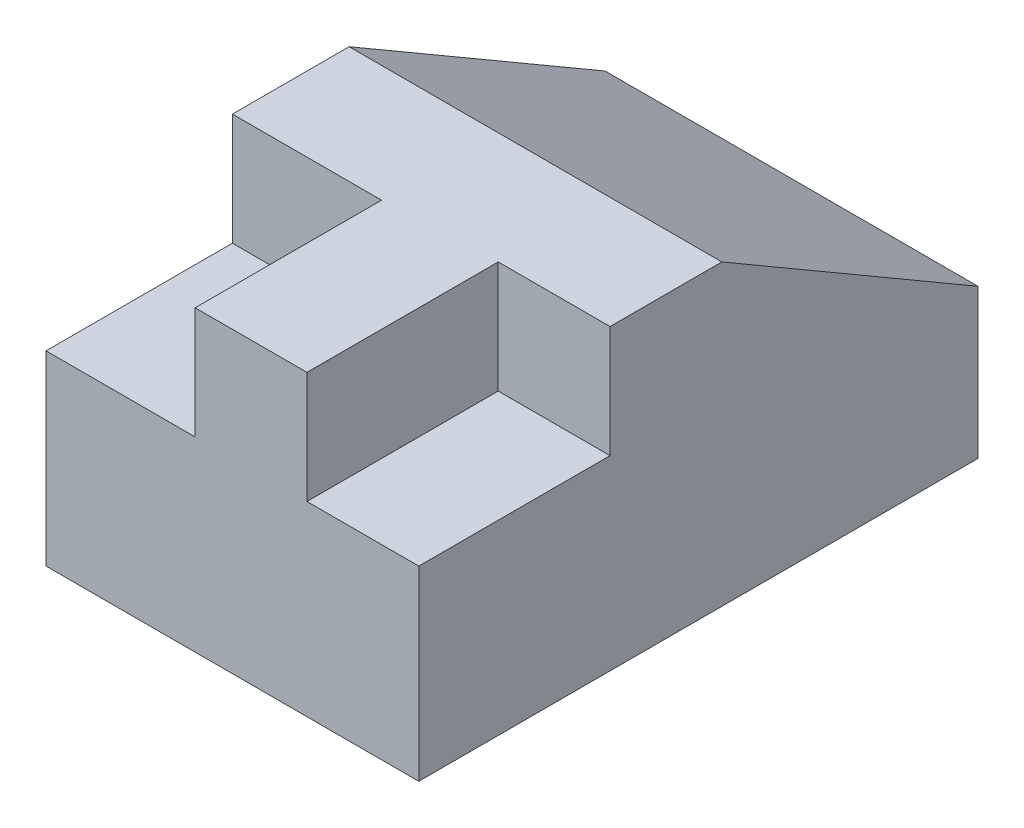
SolidWorks part; units mm, degrees
ref_plane "Front Plane" through (0, 0, 0) normal (0, 0, 1) x (1, 0, 0)
ref_plane "Top Plane" through (0, 0, 0) normal (0, 1, 0) x (1, 0, 0)
ref_plane "Right Plane" through (0, 0, 0) normal (1, 0, 0) x (0, 0, -1)
sketch "Sketch3" plane through (0, 0, 0) normal (0, 1, 0) x (1, 0, 0)
  line L1 (50, -75) -> (-50, -75)
  line L2 (50, -75) -> (50, 75)
  line L3 (50, 75) -> (-50, 75)
  line L4 (-50, -75) -> (-50, 75)
  point P0 (0, 0)
  dimension "D1" = 100
  dimension "D2" = 150
  dimension "D3" = 50
  dimension "D4" = 75
extrude "Boss-Extrude2" add sketch "Sketch3" along normal blind 80
sketch "Sketch4" plane through (50, 0, 0) normal (1, 0, 0) x (0, 0, -1)
  line L0 (-75, 80) -> (-75, 50)
  line L1 (-75, 80) -> (-75, 0) construction
  line L2 (-75, 50) -> (-23.6959, 50)
  line L3 (-23.6959, 50) -> (-23.6959, 80)
  line L4 (-75, 80) -> (75, 80) construction
  line L5 (-23.6959, 80) -> (6.3041, 80)
  line L6 (6.3041, 80) -> (75, 40)
  line L7 (75, 80) -> (75, 0) construction
  line L8 (75, 40) -> (75, 0)
  line L9 (75, 0) -> (-75, 0)
  line L10 (-75, 0) -> (-75, 50)
  line M6 (75, 0) -> (75, 80)
  line M7 (75, 80) -> (-75, 80)
  line M8 (-75, 80) -> (-75, 0)
  dimension "D1" = 50
  dimension "D2" = 30
  dimension "D3" = 79.493
extrude "Cut-Extrude4" cut sketch "Sketch4" against normal blind 100 contours L6 M7 M6 region at (50, 66.6667, -52.1014)
extrude "Cut-Extrude5" cut sketch "Sketch4<5>" against normal blind 30 and the other way through all contours L2 L3 M7 M8 region at (50, 65, 49.348)
sketch "Sketch4<5>" plane through (50, 0, 0) normal (1, 0, 0) x (0, 0, -1) same geometry as "Sketch4"
sketch "Sketch6" plane through (0, 80, 0) normal (0, 1, 0) x (1, 0, 0)
  line L0 (-50, -75) -> (-10, -75)
  line L1 (50, -75) -> (-50, -75) construction
  line L2 (-10, -75) -> (-10, -25)
  line L3 (-10, -25) -> (-50, -25)
  line L4 (-50, -75) -> (-50, 75) construction
  line L5 (-50, -25) -> (-50, -75)
  dimension "D1" = 40
  dimension "D2" = 50
extrude "Cut-Extrude6" cut sketch "Sketch6" against normal blind 30
